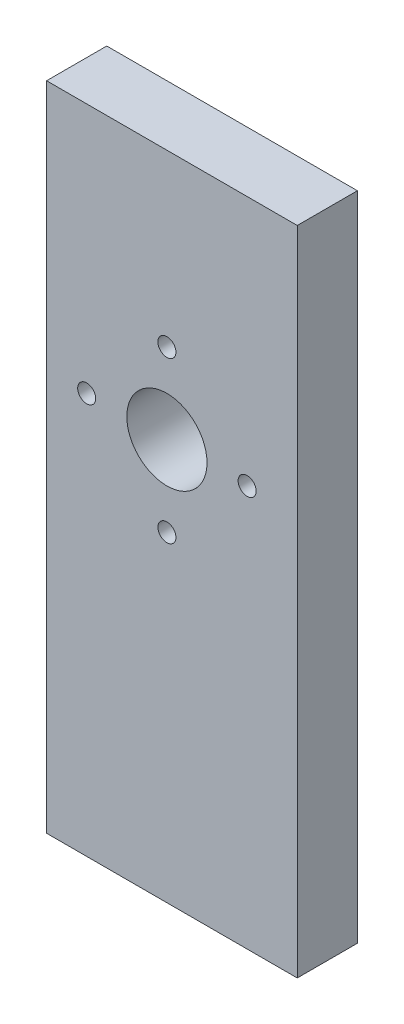
SolidWorks part; units mm, degrees
ref_plane "Plan de face" through (0, 0, 0) normal (0, 0, 1) x (1, 0, 0)
ref_plane "Plan de dessus" through (0, 0, 0) normal (0, 1, 0) x (1, 0, 0)
ref_plane "Plan de droite" through (0, 0, 0) normal (1, 0, 0) x (0, 0, -1)
sketch "Esquisse1" plane through (0, 0, 0) normal (0, 0, 1) x (1, 0, 0)
  line L0 (25.3646, -115.6707) -> (25.3646, -50.6707)
  line L1 (50.3646, -50.6707) -> (25.3646, -50.6707)
  line L2 (50.3646, -50.6707) -> (50.3646, -115.6707)
  line L3 (50.3646, -115.6707) -> (25.3646, -115.6707)
  circle A2 centre (29.3646, -75.6707) radius 0.9
  circle A3 centre (37.3646, -67.6707) radius 0.9
  circle A4 centre (45.3646, -75.6707) radius 0.9
  circle A5 centre (37.3646, -83.6707) radius 0.9
  circle A7 centre (37.3646, -75.6707) radius 4
  dimension "D3" = 25
  dimension "D11" = 25
  dimension "D10" = 13
  dimension "D6" = 1.8
  dimension "D7" = 1.8
  dimension "D8" = 1.8
  dimension "D9" = 1.8
  dimension "D4" = 8
  dimension "D1" = 65
  dimension "D2" = 65
  dimension "D5" = 25
extrude "Boss.-Extru.1" add sketch "Esquisse1" along normal blind 6
sketch "Esquisse4" plane through (25.3646, 0, 0) normal (-1, 0, 0) x (0, 0, 1)
  line L0 (6, -50.6707) -> (6, -115.6707) construction
  line L3 (6, -50.6707) -> (0, -50.6707) construction
  line L4 (6, -115.6707) -> (0, -115.6707) construction
  circle A0 centre (3, -55.6707) radius 1.5
  circle A1 centre (3, -110.6707) radius 1.5
  point P6 (3, -50.6707)
  point P8 (-3.557, -56.7405)
  dimension "D1" = 3
  dimension "D2" = 3
  dimension "D3" = 3
  dimension "D4" = 3
  dimension "D5" = 5
  dimension "D6" = 5
extrude "Enlèv. mat.-Extru.3" cut sketch "Esquisse4" against normal blind 10
